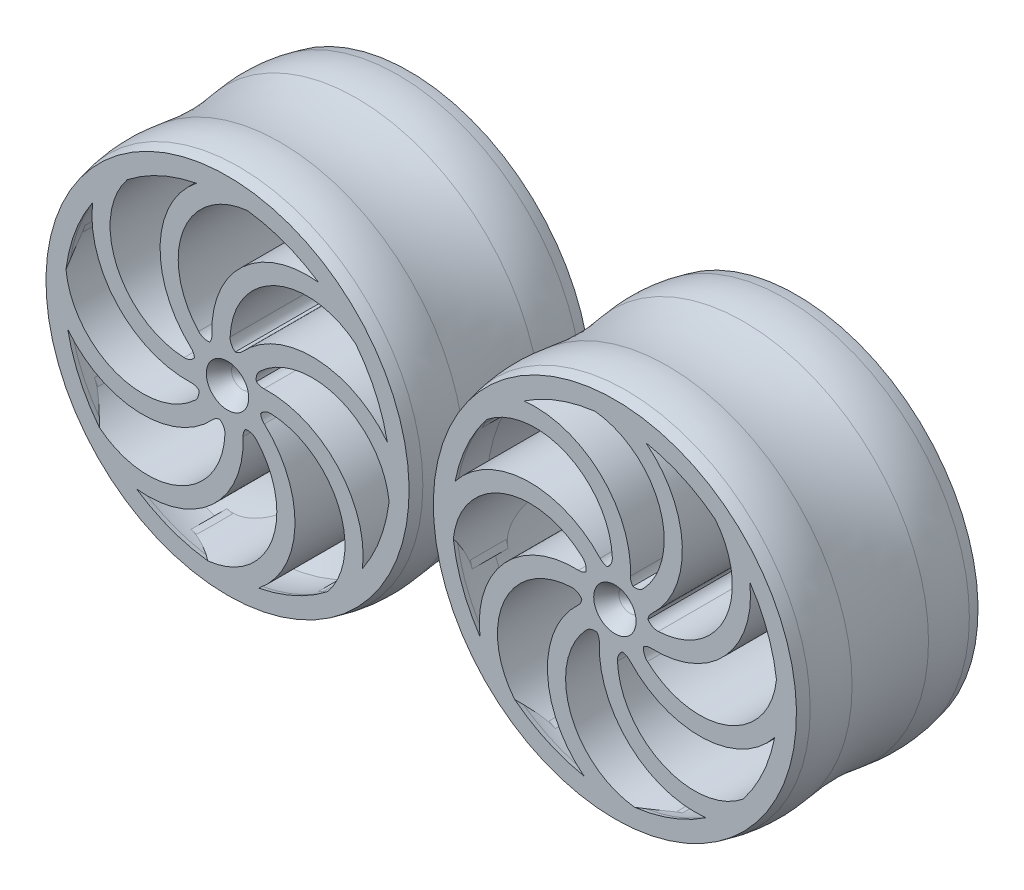
SolidWorks part; units mm, degrees
ref_plane "Front Plane" through (0, 0, 0) normal (0, 0, 1) x (1, 0, 0)
ref_plane "Top Plane" through (0, 0, 0) normal (0, 1, 0) x (1, 0, 0)
ref_plane "Right Plane" through (0, 0, 0) normal (1, 0, 0) x (0, 0, -1)
sketch "Sketch1" plane through (0, 0, 0) normal (1, 0, 0) x (0, 0, -1)
  line L0 (-7.5, 0.75) -> (7.5, 0.75)
  line L2 (-7.5, 0.75) -> (-7.5, 15)
  line L4 (7.5, 0.75) -> (7.5, 15)
  line L5 (-7.5, 0) -> (7.5, 0) construction
  line L6 (-7.1098, 13.5516) -> (-7.5, 13.4465)
  line L8 (7.1098, 13.5516) -> (7.5, 13.4465)
  line L9 (-7.5, 2.75) -> (7.5, 2.75)
  circle A0 centre (0, 34.85) radius 20 construction
  arc A1 (-4, 15.4072) -> (4, 15.4072) centre (0, 34.85) ccw
  arc A4 (-7.5, 15) -> (-4, 15.4072) centre (-4.3783, 3.4132) cw
  arc A5 (4, 15.4072) -> (7.5, 15) centre (4.3783, 3.4132) cw
  arc A9 (-7.1098, 13.5516) -> (-4.1695, 13.9111) centre (-4.3783, 3.4132) cw
  arc A10 (-4.1695, 13.9111) -> (4.1695, 13.9111) centre (0, 34.85) ccw
  arc A11 (4.1695, 13.9111) -> (7.1098, 13.5516) centre (4.3783, 3.4132) cw
  point P11 (0, 15)
  point P15 (0, 0.75)
  point P16 (0, 0)
  dimension "D3" = 40
  dimension "D4" = 19.85
  dimension "D5" = 8
  dimension "D7" = 12
  dimension "D8" = 12
  dimension "D11" = 1.5
  dimension "D1" = 15
  dimension "D2" = 0.75
  dimension "D6" = 15
  dimension "D9" = 15
  dimension "D10" = 14.25
  dimension "D12" = 0.3902
  dimension "D13" = 2
revolve "Revolve1" add sketch "Sketch1" angle 360 about L5 region at (0, 1.75, 0) region at (0, 14.4509, 0)
ref_plane "Plane4" through (0, 0, 0) normal (0, 0, -1) x (-1, 0, 0)
sketch "Sketch3" plane through (0, 0, 0) normal (0, 0, -1) x (-1, 0, 0)
  line L0 (13.2364, 4.4994) -> (13.9713, -0.5006) construction
  line L1 (11.9741, 4.4994) -> (15.2336, -0.5006) construction
  circle A0 centre (0, 0) radius 13.75
  circle A1 centre (0, 0) radius 1
  arc A2 (0.9501, -0.312) -> (13.0636, -4.2902) centre (7.0068, -2.3011) cw
  arc A3 (0.5942, 0.8043) -> (13.75, 0) centre (7.0068, -2.3011) cw construction
  arc A4 (-0.148, 0.989) -> (13.6038, 1.9994) centre (7.0068, -2.3011) cw
  arc A5 (0.5947, 0.8039) -> (11.0332, -8.2056) centre (3.3274, -6.5817) cw
  arc A6 (0.9889, 0.1486) -> (9.7227, -9.7227) centre (3.3274, -6.5817) cw construction
  arc A7 (0.4512, -0.8924) -> (6.2037, -12.271) centre (3.3274, -6.5817) cw
  arc A8 (0.989, 0.148) -> (1.9994, -13.6038) centre (-2.3011, -7.0068) cw
  arc A9 (0.8043, -0.5942) -> (0, -13.75) centre (-2.3011, -7.0068) cw construction
  arc A10 (-0.312, -0.9501) -> (-4.2902, -13.0636) centre (-2.3011, -7.0068) cw
  arc A11 (0.8039, -0.5947) -> (-8.2056, -11.0332) centre (-6.5817, -3.3274) cw
  arc A12 (0.1486, -0.9889) -> (-9.7227, -9.7227) centre (-6.5817, -3.3274) cw construction
  arc A13 (-0.8924, -0.4512) -> (-12.271, -6.2037) centre (-6.5817, -3.3274) cw
  arc A14 (0.148, -0.989) -> (-13.6038, -1.9994) centre (-7.0068, 2.3011) cw
  arc A15 (-0.5942, -0.8043) -> (-13.75, 0) centre (-7.0068, 2.3011) cw construction
  arc A16 (-0.9501, 0.312) -> (-13.0636, 4.2902) centre (-7.0068, 2.3011) cw
  arc A17 (-0.5947, -0.8039) -> (-11.0332, 8.2056) centre (-3.3274, 6.5817) cw
  arc A18 (-0.9889, -0.1486) -> (-9.7227, 9.7227) centre (-3.3274, 6.5817) cw construction
  arc A19 (-0.4512, 0.8924) -> (-6.2037, 12.271) centre (-3.3274, 6.5817) cw
  arc A20 (-0.989, -0.148) -> (-1.9994, 13.6038) centre (2.3011, 7.0068) cw
  arc A21 (-0.8043, 0.5942) -> (0, 13.75) centre (2.3011, 7.0068) cw construction
  arc A22 (0.312, 0.9501) -> (4.2902, 13.0636) centre (2.3011, 7.0068) cw
  arc A23 (-0.8039, 0.5947) -> (8.2056, 11.0332) centre (6.5817, 3.3274) cw
  arc A24 (-0.1486, 0.9889) -> (9.7227, 9.7227) centre (6.5817, 3.3274) cw construction
  arc A25 (0.8924, 0.4512) -> (12.271, 6.2037) centre (6.5817, 3.3274) cw
  point P10 (0, 0)
  point P16 (13.6038, 1.9994)
  point P20 (0, 0)
  point P21 (0, 0)
  point P32 (13.6038, 1.9994)
  point P81 (0, 0)
  point P86 (0, 0)
  point P87 (0, 0)
  dimension "D1" = 27.5
  dimension "D2" = 2
  dimension "D4" = 0.75
  dimension "D5" = 7.125
  dimension "D3" = 1.5
  dimension "D6" = 5
  dimension "D7" = 24.739
  dimension "D8" = 8
extrude "Boss-Extrude1" add sketch "Sketch3" along normal up to surface and the other way up to surface contours A2 A8 A7 A0 A5 | A25 A5 A2 A0 A4 | A4 A25 A0 A23 A22 | A19 A23 A22 A0 A20 | A16 A20 A19 A0 A17 | A13 A17 A16 A0 A14 | A10 A14 A13 A0 A11 | A7 A11 A10 A0 A8 region at (-13.4131, -2.1461, 0) region at (-4.3694, 9.4863, 0) region at (-8.746, -10.3898, 0) region at (3.6156, 9.7963, 0) region at (1.1626, -13.5339, 0) region at (9.4863, 4.3694, 0) region at (10.3898, -8.746, 0) region at (9.7963, -3.6156, 0) up to face at (0, -15, -7.5) other way up to face at (0, -15, 7.5)
fillet "Fillet3" radius 1 16 edges at (-2.74, -0.2338, 0) (-2.614, -0.854, 0) (-1.7722, -2.1028, 0) (-1.2445, -2.4523, 0) (0.2338, -2.74, 0) (0.854, -2.614, 0) (2.1028, -1.7722, 0) (2.4523, -1.2445, 0) (2.74, 0.2338, 0) (2.614, 0.854, 0) (1.7722, 2.1028, 0) (1.2445, 2.4523, 0) (-0.2338, 2.74, 0) (-0.854, 2.614, 0) (-2.1028, 1.7722, 0) (-2.4523, 1.2445, 0)
ref_plane "Plane5" through (-16, 0, 0) normal (1, 0, 0) x (0, 0, -1)
fillet "Fillet4" radius 10 2 edges at (0, -15.4072, 4) (0, -15.4072, -4)
chamfer "Chamfer4" distance 1 distance2 1.5 1 edges at (0, -0.75, 7.5) first distance on face at (-0.2038, -7.2131, 7.5)
fillet "Fillet9" radius 1 1 edges at (0, -0.75, 6)
mirror "Mirror2" about plane through (-16, 0, 0) normal (1, 0, 0) of bodies 103
